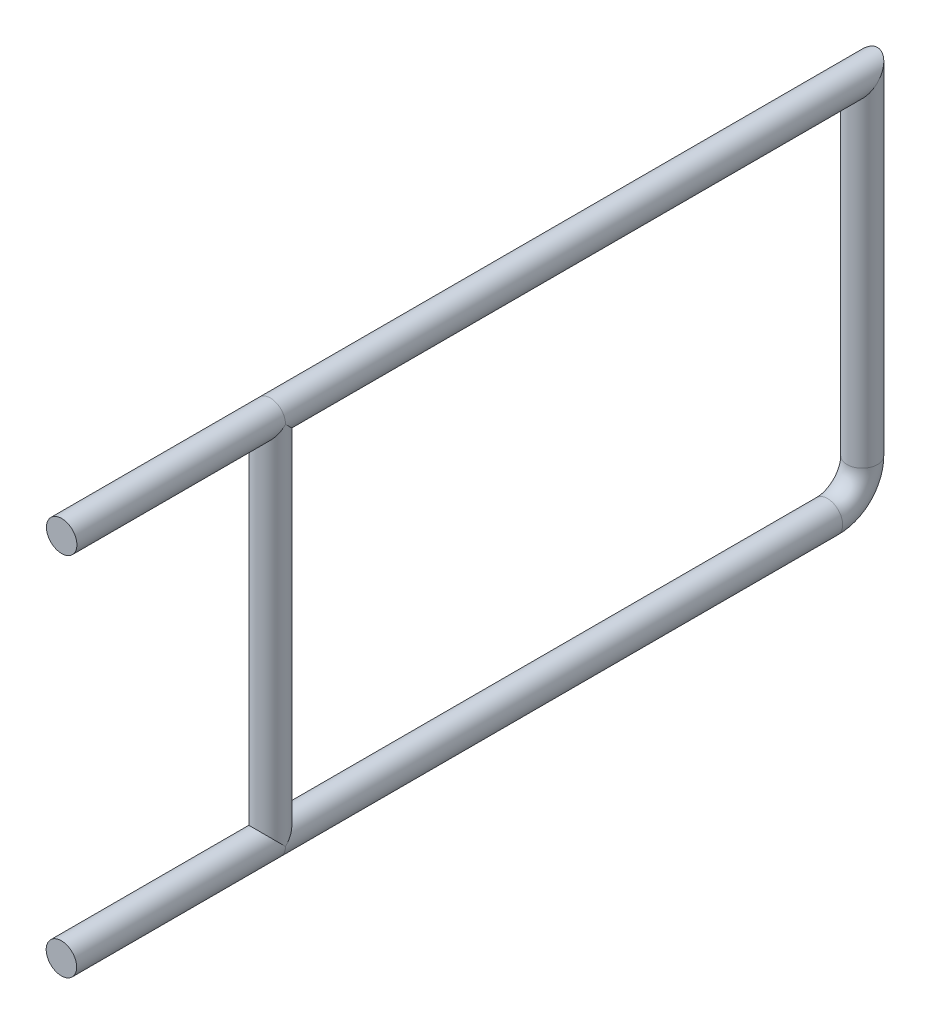
SolidWorks part; units mm, degrees
note: The reader was unsure of these and kept them because the rebuilt part matched: shared geometry of "Sketch3<8>", "Sketch1<23>".
ref_plane "Front Plane" through (0, 0, 0) normal (0, 0, 1) x (1, 0, 0)
ref_plane "Top Plane" through (0, 0, 0) normal (0, 1, 0) x (1, 0, 0)
ref_plane "Right Plane" through (0, 0, 0) normal (1, 0, 0) x (0, 0, -1)
sketch "Sketch1" plane through (0, 0, 0) normal (1, 0, 0) x (0, 0, -1)
  line L0 (126.1633, -30.1592) -> (152.2128, -152.4)
  line L2 (152.2128, -431.8) -> (584.0128, -431.8)
  line L4 (584.0128, -673.1) -> (584.0128, -431.8)
  line L5 (152.2128, -431.8) -> (0, -431.8)
  line L6 (558.6128, -698.5) -> (152.2128, -698.5)
  line L7 (88.9, 0) -> (0, 0)
  line L8 (152.2128, -152.4) -> (431.6128, -152.4)
  line L10 (457.0128, -177.8) -> (457.0128, -273.05)
  line L16 (457.0128, -273.05) -> (558.6128, -273.05)
  line L17 (584.0128, -298.45) -> (584.0128, -431.8)
  line L18 (-0.1872, -698.5) -> (152.2128, -698.5)
  line L19 (152.2128, -698.5) -> (152.2128, -431.8)
  line L20 (152.2128, -152.4) -> (152.2128, -431.8)
  arc A0 (88.9, 0) -> (126.1633, -30.1592) centre (88.9, -38.1) cw
  arc A1 (584.0128, -673.1) -> (558.6128, -698.5) centre (558.6128, -673.1) cw
  arc A2 (584.0128, -298.45) -> (558.6128, -273.05) centre (558.6128, -298.45) ccw
  arc A3 (431.6128, -152.4) -> (457.0128, -177.8) centre (431.6128, -177.8) cw
  point P5 (584.0128, -698.5)
  point P24 (584.0128, -273.05)
  point P30 (457.0128, -152.4)
  dimension "D2" = 38.1
  dimension "D11" = 25.4
  dimension "D9" = 25.4
  dimension "D1" = 88.9
  dimension "D3" = 120.65
  dimension "D4" = 431.8
  dimension "D5" = 431.8
  dimension "D6" = 279.4
  dimension "D7" = 152.4
  dimension "D8" = 546.1
  dimension "D10" = 127
  dimension "D17" = 124.9856
sketch "Sketch3" plane through (0, 0, 0) normal (0, 0, 1) x (1, 0, 0)
  circle A0 centre (0, -698.5) radius 11.1125
  dimension "D1" = 22.225
sweep "Sweep1" add profiles "Sketch3" path "Sketch1"
sweep "Sweep2" add profiles "Sketch3<8>" path "Sketch1<23>"
sketch "Sketch3<8>" plane through (0, 0, 0) normal (0, 0, 1) x (1, 0, 0) same geometry as "Sketch3"
sketch "Sketch1<23>" plane through (0, 0, 0) normal (1, 0, 0) x (0, 0, -1) same geometry as "Sketch1"
sketch "Sketch10" plane through (0, 0, 0) normal (1, 0, 0) x (0, 0, -1)
  line L1 (152.4, -914.4) -> (-272.7134, -914.4)
  line L2 (152.2128, -698.5) -> (152.2128, -431.8) construction
  circle A0 centre (152.2128, -609.6) radius 304.8
  dimension "D1" = 609.6
  dimension "D2" = 88.9
sketch "Sketch11" plane through (0, 0, 0) normal (1, 0, 0) x (0, 0, -1)
  line L0 (584.0128, -647.7) -> (152.2128, -647.7)
  line L1 (584.0128, -673.1) -> (584.0128, -431.8) construction
  line L2 (152.2128, -698.5) -> (152.2128, -431.8) construction
  line L3 (152.2128, -647.7) -> (152.2128, -698.5)
  line L4 (152.2128, -698.5) -> (558.6128, -698.5)
  line L5 (584.0128, -673.1) -> (584.0128, -647.7)
  line L6 (584.0128, -431.8) -> (584.0128, -482.6)
  line L7 (584.0128, -482.6) -> (152.2128, -482.6)
  line L8 (152.2128, -482.6) -> (152.2128, -431.8)
  line L9 (152.2128, -431.8) -> (584.0128, -431.8)
  line L10 (380.8128, -463.55) -> (177.6128, -666.75) construction
  line L11 (389.793, -472.5303) -> (186.593, -675.7303)
  line L12 (371.8325, -454.5697) -> (168.6325, -657.7697)
  line L13 (380.8128, -666.75) -> (177.6128, -463.55) construction
  line L14 (371.8325, -675.7303) -> (168.6325, -472.5303)
  line L15 (389.793, -657.7697) -> (186.593, -454.5697)
  line L16 (380.8128, -463.55) -> (507.8128, -463.55) construction
  line L17 (380.8128, -450.85) -> (507.8128, -450.85)
  line L18 (380.8128, -476.25) -> (507.8128, -476.25)
  line L19 (380.8128, -666.75) -> (507.8128, -666.75) construction
  line L20 (380.8128, -654.05) -> (507.8128, -654.05)
  line L21 (380.8128, -679.45) -> (507.8128, -679.45)
  line L22 (177.6128, -463.55) -> (177.6128, -666.75) construction
  line L23 (177.6128, -565.15) -> (446.4211, -666.75) construction
  line L24 (177.6128, -666.75) -> (446.4211, -565.15) construction
  line L25 (177.6128, -532.9233) -> (431.9175, -666.75) construction
  line L26 (431.9175, -666.75) -> (431.9175, -532.9233) construction
  line L27 (431.9175, -532.9233) -> (177.6128, -666.75) construction
  arc A0 (584.0128, -673.1) -> (558.6128, -698.5) centre (558.6128, -673.1) cw
  circle A1 centre (177.6128, -463.55) radius 6.35
  circle A2 centre (177.6128, -666.75) radius 6.35
  circle A3 centre (279.2128, -565.15) radius 6.35
  arc A4 (380.8128, -450.85) -> (380.8128, -476.25) centre (380.8128, -463.55) ccw
  arc A5 (389.793, -472.5303) -> (371.8325, -454.5697) centre (380.8128, -463.55) ccw
  arc A6 (168.6325, -657.7697) -> (186.593, -675.7303) centre (177.6128, -666.75) ccw
  arc A7 (371.8325, -675.7303) -> (389.793, -657.7697) centre (380.8128, -666.75) ccw
  arc A8 (186.593, -454.5697) -> (168.6325, -472.5303) centre (177.6128, -463.55) ccw
  arc A9 (507.8128, -476.25) -> (507.8128, -450.85) centre (507.8128, -463.55) ccw
  arc A10 (380.8128, -654.05) -> (380.8128, -679.45) centre (380.8128, -666.75) ccw
  arc A11 (507.8128, -679.45) -> (507.8128, -654.05) centre (507.8128, -666.75) ccw
  arc A12 (380.8128, -463.55) -> (464.982, -666.75) centre (177.6064, -666.7541) cw
  circle A13 centre (380.8128, -463.55) radius 6.35
  circle A14 centre (380.8128, -666.75) radius 6.35
  point P12 (584.0128, -698.5)
  point P27 (279.2128, -565.15)
  point P32 (279.2128, -565.15)
  point P39 (444.3128, -463.55)
  point P44 (444.3128, -666.75)
  dimension "D1" = 25.4
  dimension "D4" = 12.7
  dimension "D5" = 12.7
  dimension "D8" = 12.7
  dimension "D12" = 287.3756
  dimension "D2" = 50.8
  dimension "D3" = 50.8
  dimension "D6" = 19.05
  dimension "D7" = 19.05
  dimension "D9" = 90
  dimension "D10" = 25.4
  dimension "D11" = 76.2
